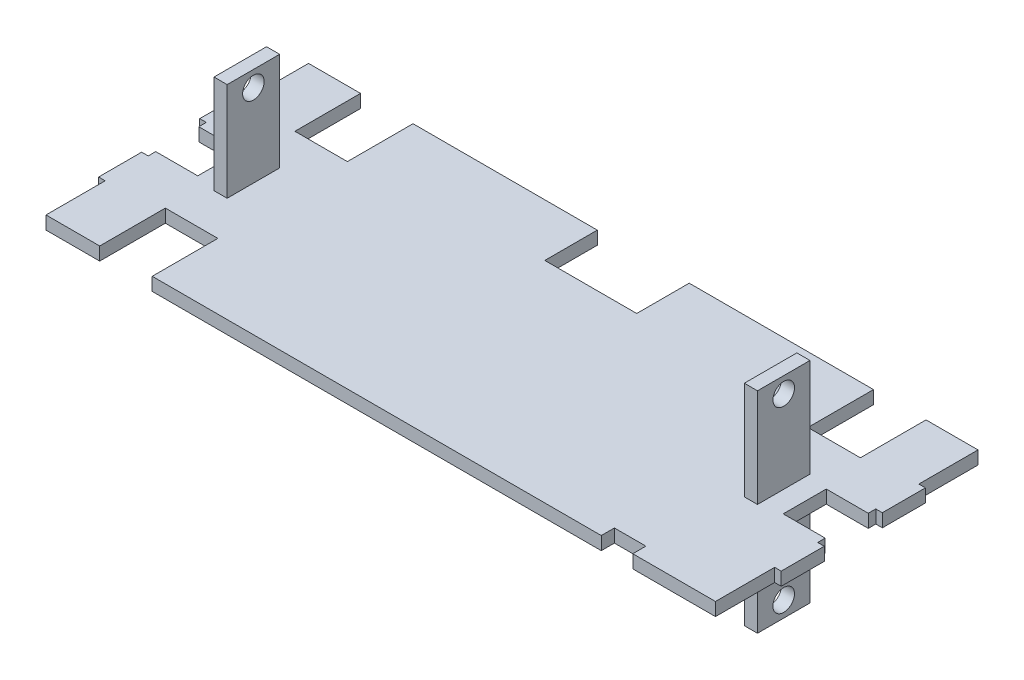
SolidWorks part; units mm, degrees
ref_plane "Front Plane" through (0, 0, 0) normal (0, 0, 1) x (1, 0, 0)
ref_plane "Top Plane" through (0, 0, 0) normal (0, 1, 0) x (1, 0, 0)
ref_plane "Right Plane" through (0, 0, 0) normal (1, 0, 0) x (0, 0, -1)
sketch "Sketch1" plane through (0, 0, 0) normal (0, 1, 0) x (1, 0, 0)
  line L1 (161.925, -63.5) -> (121.92, -63.5)
  line L2 (161.925, -63.5) -> (161.925, -34.8747)
  line L3 (161.925, 63.5) -> (136.779, 63.5)
  line L4 (-161.925, -63.5) -> (-161.925, -34.8747)
  line L5 (161.925, -63.5) -> (-161.925, 63.5) construction
  line L6 (161.925, 63.5) -> (-161.925, -63.5) construction
  line L7 (161.925, 10.414) -> (141.605, 10.414)
  line L9 (161.925, -10.414) -> (141.605, -10.414)
  line L10 (141.605, 10.414) -> (141.605, -10.414)
  line L11 (-136.779, 63.5) -> (-161.925, 63.5)
  line L13 (-161.925, -10.414) -> (-141.605, -10.414)
  line L14 (-141.605, 10.414) -> (-141.605, -10.414)
  line L15 (-161.925, 10.414) -> (-141.605, 10.414)
  line L17 (-141.605, 0) -> (127, 0) construction
  line L18 (-161.925, 14.0467) -> (-165.1, 14.0467)
  line L20 (-161.925, 34.8747) -> (-165.1, 34.8747)
  line L21 (-165.1, 14.0467) -> (-165.1, 34.8747)
  line L22 (-161.925, -34.8747) -> (-165.1, -34.8747)
  line L23 (-165.1, -14.0467) -> (-165.1, -34.8747)
  line L24 (-161.925, -14.0467) -> (-165.1, -14.0467)
  line L27 (161.925, -14.0467) -> (165.1, -14.0467)
  line L28 (165.1, -14.0467) -> (165.1, -34.8747)
  line L29 (161.925, -34.8747) -> (165.1, -34.8747)
  line L30 (161.925, 34.8747) -> (165.1, 34.8747)
  line L31 (165.1, 14.0467) -> (165.1, 34.8747)
  line L32 (161.925, 14.0467) -> (165.1, 14.0467)
  line L34 (-161.925, 34.8747) -> (-161.925, 63.5)
  line L35 (-161.925, -14.0467) -> (-161.925, -10.414)
  line L36 (161.925, 34.8747) -> (161.925, 63.5)
  line L37 (161.925, -14.0467) -> (161.925, -10.414)
  line L38 (-161.925, 10.414) -> (-161.925, 14.0467)
  line L39 (161.925, 10.414) -> (161.925, 14.0467)
  line L40 (-136.779, 63.5) -> (-136.779, 31.75)
  line L41 (-136.779, 31.75) -> (-111.379, 31.75)
  line L42 (-111.379, 63.5) -> (-111.379, 31.75)
  line L44 (111.379, 63.5) -> (111.379, 31.75)
  line L45 (111.379, 31.75) -> (136.779, 31.75)
  line L46 (136.779, 63.5) -> (136.779, 31.75)
  line L47 (111.379, 63.5) -> (22.2286, 63.5)
  line L48 (106.68, -63.5) -> (-106.68, -63.5)
  line L50 (106.68, -63.5) -> (106.68, -57.15)
  line L51 (106.68, -57.15) -> (121.92, -57.15)
  line L52 (121.92, -63.5) -> (121.92, -57.15)
  line L56 (-135.9408, -63.5) -> (-161.925, -63.5)
  line L57 (-106.68, -63.5) -> (-110.5408, -63.5)
  line L59 (-135.9408, -63.5) -> (-135.9408, -31.75)
  line L60 (-135.9408, -31.75) -> (-110.5408, -31.75)
  line L61 (-110.5408, -63.5) -> (-110.5408, -31.75)
  line L62 (-22.2286, 63.5) -> (-111.379, 63.5)
  line L64 (22.2286, 63.5) -> (22.2286, 38.1)
  line L65 (22.2286, 38.1) -> (-22.2286, 38.1)
  line L66 (-22.2286, 63.5) -> (-22.2286, 38.1)
  line L69 (0, 38.1) -> (0, -76.3761) construction
  point P0 (0, 0)
  point P6 (141.605, 0)
  point P47 (121.92, -60.325)
  point P48 (124.079, 31.75)
  point P49 (-124.079, 31.75)
  point P50 (0, 63.5)
  point P52 (-123.2408, -31.75)
  dimension "D1" = 323.85
  dimension "D2" = 127
  dimension "D3" = 20.828
  dimension "D5" = 3.175
  dimension "D6" = 20.828
  dimension "D4" = 20.32
  dimension "D7" = 31.75
  dimension "D8" = 25.4
  dimension "D9" = 25.4
  dimension "D10" = 31.75
  dimension "D13" = 15.24
  dimension "D14" = 6.35
  dimension "D15" = 40.005
  dimension "D16" = 25.4
  dimension "D17" = 31.75
  dimension "D18" = 41.8592
  dimension "D11" = 41.021
  dimension "D12" = 41.021
  dimension "D19" = 25.4
  dimension "D20" = 44.4572
extrude "Boss-Extrude1" add sketch "Sketch1" along normal mid plane 6.35
sketch "Sketch2" plane through (0, 0, 0) normal (0, 1, 0) x (1, 0, 0)
  line L0 (-141.605, 10.414) -> (-141.605, -10.414) construction
  line L1 (125.095, -12.7) -> (131.445, -12.7)
  line L2 (125.095, -12.7) -> (125.095, 12.7)
  line L3 (125.095, 12.7) -> (131.445, 12.7)
  line L4 (131.445, -12.7) -> (131.445, 12.7)
  line L5 (125.095, -12.7) -> (131.445, 12.7) construction
  line L6 (125.095, 12.7) -> (131.445, -12.7) construction
  line L9 (-125.095, -12.7) -> (-125.095, 12.7)
  line L10 (-125.095, 12.7) -> (-131.445, 12.7)
  line L11 (-131.445, -12.7) -> (-131.445, 12.7)
  line L12 (-125.095, -12.7) -> (-131.445, -12.7)
  line L13 (141.605, -10.414) -> (141.605, 10.414) construction
  point P0 (128.27, 0)
  point P10 (141.605, 0)
  dimension "D1" = 10.16
  dimension "D2" = 10.16
  dimension "D3" = 25.4
  dimension "D4" = 25.4
  dimension "D5" = 6.35
  dimension "D6" = 6.35
  dimension "D7" = 6.35
extrude "Boss-Extrude2" add sketch "Sketch2" along normal mid plane 101.6
sketch "Sketch3" plane through (-131.445, 0, 0) normal (-1, 0, 0) x (0, 0, 1)
  line L0 (-12.7, 50.8) -> (12.7, 50.8) construction
  line L1 (-12.7, -50.8) -> (12.7, -50.8) construction
  circle A0 centre (0, 43.18) radius 5.207
  circle A1 centre (0, -43.18) radius 5.207
  point P4 (0, 50.8)
  dimension "D1" = 10.414
  dimension "D2" = 10.414
  dimension "D3" = 7.62
  dimension "D4" = 7.62
  dimension "D5" = 86.36
extrude "Cut-Extrude1" cut sketch "Sketch3" against normal through all both and the other way through all
equation "\"length\"= 12.75"
equation "\"width\"=5"
equation "\"height\"= 0.25"
equation "\"D1@Sketch1\"=\"length\""
equation "\"D2@Sketch1\"=\"width\""
equation "\"eyebolt width\"= 0.82"
equation "\"eyebolt length\"= 0.8"
equation "\"D3@Sketch1\"=\"eyebolt width\""
equation "\"D4@Sketch1\"=\"eyebolt length\""
equation "\"lead screw holder height\"= 2.76"
equation "\"lead screw diameter\"=0.41"
equation "\"D1@Sketch3\"=\"lead screw diameter\""
equation "\"distance from holders to board\"=0.4"
equation "\"D2@Sketch3\"=\"lead screw diameter\""
equation "\"lead_screw_dist\"=3.4"
equation "\"D5@Sketch3\"=\"lead_screw_dist\""
